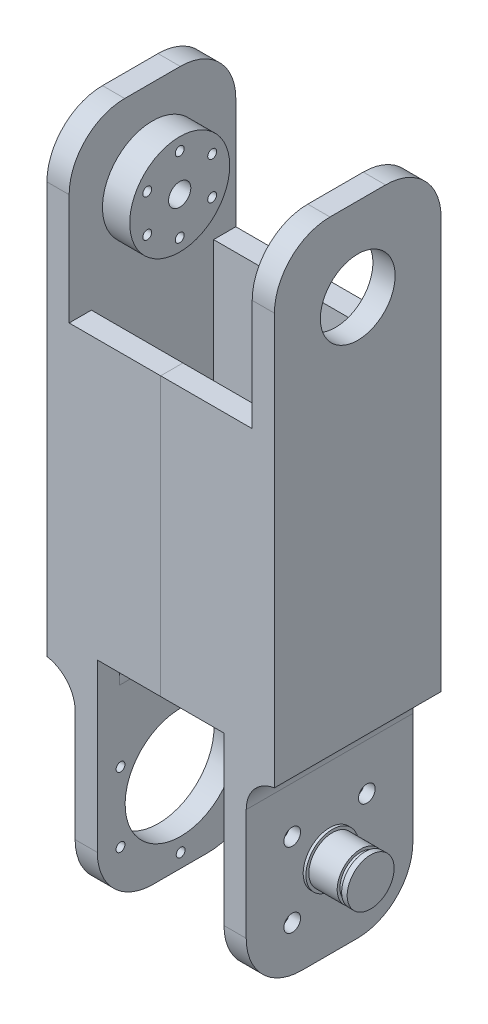
SolidWorks part; units mm, degrees
ref_plane "前视基准面" through (0, 0, 0) normal (0, 0, 1) x (1, 0, 0)
ref_plane "上视基准面" through (0, 0, 0) normal (0, 1, 0) x (1, 0, 0)
ref_plane "右视基准面" through (0, 0, 0) normal (1, 0, 0) x (0, 0, -1)
other "Configuration Table"
sketch "草图1" plane through (0, 0, 0) normal (1, 0, 0) x (0, 0, -1)
  line L1 (30, -80) -> (-30, -80)
  line L2 (30, -80) -> (30, 80)
  line L3 (30, 80) -> (-30, 80)
  line L4 (-30, -80) -> (-30, 80)
  line L5 (30, -80) -> (-30, 80) construction
  line L6 (30, 80) -> (-30, -80) construction
  point P0 (0, 0)
  dimension "D1" = 160
  dimension "D2" = 60
extrude "凸台-拉伸1" add sketch "草图1" along normal blind 8
sketch "草图2" plane through (8, 0, 0) normal (1, 0, 0) x (0, 0, -1)
  line L1 (30, 80) -> (-30, 80) construction
  circle A0 centre (0, 50) radius 13.5 construction
  circle A2 centre (0, 63.5) radius 1.6
  circle A4 centre (11.6913, 56.75) radius 1.6
  circle A5 centre (11.6913, 43.25) radius 1.6
  circle A6 centre (0, 36.5) radius 1.6
  circle A7 centre (-11.6913, 43.25) radius 1.6
  circle A8 centre (-11.6913, 56.75) radius 1.6
  circle A12 centre (0, 50) radius 4
  point P6 (0, 80)
  point P26 (0, 50)
  dimension "D3" = 27
  dimension "D7" = 3.2
  dimension "D11" = 8
  dimension "D2" = 30
  dimension "D9" = 6
extrude "切除-拉伸1" cut sketch "草图2" against normal through all
sketch "草图20" plane through (8, 0, 0) normal (1, 0, 0) x (0, 0, -1)
  circle A0 centre (0, 50) radius 18
  dimension "D1" = 36
extrude "凸台-拉伸7" add sketch "草图20" along normal blind 9.8
sketch "草图3" plane through (8, 0, 0) normal (1, 0, 0) x (0, 0, -1)
  line L0 (-30, 80) -> (-30, -80) construction
  line L1 (-22, -80) -> (-30, -80)
  line L2 (-22, -80) -> (-22, 20)
  line L3 (-22, 20) -> (-30, 20)
  line L4 (-30, -80) -> (-30, 20)
  line L5 (-22, -80) -> (-30, 20) construction
  line L6 (-22, 20) -> (-30, -80) construction
  line L7 (30, -80) -> (22, -80)
  line L8 (30, -80) -> (30, 20)
  line L9 (30, 20) -> (22, 20)
  line L10 (22, -80) -> (22, 20)
  line L11 (30, -80) -> (22, 20) construction
  line L12 (30, 20) -> (22, -80) construction
  line L13 (30, -80) -> (30, 80) construction
  line L14 (30, 80) -> (-30, 80) construction
  line L16 (-30, -80) -> (30, -80) construction
  point P0 (-26, -30)
  point P5 (26, -30)
  dimension "D1" = 60
  dimension "D3" = 60
  dimension "D5" = 8
  dimension "D6" = 8
extrude "凸台-拉伸2" add sketch "草图3" along normal blind 65.9
sketch "草图4" plane through (73.9, 0, 0) normal (1, 0, 0) x (0, 0, -1)
  line L0 (30, -80) -> (-30, 80) construction
  line L1 (30, -80) -> (-30, -80)
  line L2 (30, -80) -> (30, 80)
  line L3 (30, 80) -> (-30, 80)
  line L4 (-30, -80) -> (-30, 80)
  line L5 (30, -80) -> (-30, 80) construction
  line L6 (30, 80) -> (-30, -80) construction
  line L7 (30, 80) -> (-30, 80) construction
  point P0 (0, 0)
extrude "凸台-拉伸3" add sketch "草图4" along normal blind 8
sketch "草图9" plane through (73.9, 0, 0) normal (-1, 0, 0) x (0, 0, 1)
  circle A0 centre (0, 50) radius 13.45
  dimension "D1" = 26.9
extrude "切除-拉伸5" cut sketch "草图9" against normal up to next
sketch "草图11" plane through (0, 0, 30) normal (0, 0, 1) x (1, 0, 0)
  line L0 (0, 80) -> (0, -80) construction
  line L1 (0, -80) -> (18.15, -80)
  line L2 (0, -80) -> (0, -88)
  line L3 (0, -88) -> (18.15, -88)
  line L4 (18.15, -80) -> (18.15, -88)
  line L5 (81.9, -80) -> (63.75, -80)
  line L6 (81.9, -80) -> (81.9, -88)
  line L7 (81.9, -88) -> (63.75, -88)
  line L8 (63.75, -80) -> (63.75, -88)
  line L9 (81.9, 80) -> (81.9, -80) construction
  line L11 (18.15, -88) -> (10.15, -88)
  line L12 (18.15, -88) -> (18.15, -160)
  line L13 (18.15, -160) -> (10.15, -160)
  line L14 (10.15, -88) -> (10.15, -160)
  line L15 (63.75, -88) -> (71.75, -88)
  line L16 (63.75, -88) -> (63.75, -160)
  line L17 (63.75, -160) -> (71.75, -160)
  line L18 (71.75, -88) -> (71.75, -160)
  line M10 (0, -80) -> (81.9, -80)
  dimension "D1" = 8
  dimension "D2" = 8
  dimension "D3" = 45.6
  dimension "D4" = 72
  dimension "D5" = 72
  dimension "D6" = 8
  dimension "D7" = 8
extrude "凸台-拉伸4" add sketch "草图11" against normal blind 60 contours L3 L14 L13 L12 | L4 L2 L3 M10 | L8 L7 L6 M10 | L18 L7 L16 L17 region at (72.825, -84, 30) region at (9.075, -84, 30) region at (14.15, -124, 30) region at (67.75, -124, 30)
fillet "圆角1" radius 20 8 edges at (4, 80, -30) (4, 80, 30) (77.9, 80, -30) (77.9, 80, 30) (67.75, -160, -30) (67.75, -160, 30) (14.15, -160, -30) (14.15, -160, 30)
fillet "圆角2" radius 12 4 edges at (63.75, -80, 0) (18.15, -80, 0) (71.75, -88, 0) (10.15, -88, 0)
sketch "草图13" plane through (71.75, 0, 0) normal (1, 0, 0) x (0, 0, -1)
  line L0 (10, -160) -> (-10, -160) construction
  line L1 (0, -130) -> (13.435, -116.565) construction
  line L3 (0, -130) -> (0, -111) construction
  circle A0 centre (0, -130) radius 19 construction
  circle A1 centre (13.435, -116.565) radius 1.6
  circle A2 centre (13.435, -143.435) radius 1.6
  circle A3 centre (-13.435, -143.435) radius 1.6
  circle A4 centre (-13.435, -116.565) radius 1.6
  point P4 (0, -160)
  point P5 (0.0241, -160.1066)
  point P6 (0, 0)
  point P17 (0, -130)
  dimension "D1" = 38
  dimension "D3" = 3.2
  dimension "D2" = 30
  dimension "D5" = 45
  dimension "D4" = 4
extrude "切除-拉伸6" cut sketch "草图13" against normal up to next
sketch "草图12" plane through (10.15, 0, 0) normal (-1, 0, 0) x (0, 0, 1)
  circle A0 centre (0, -130) radius 25 construction
  circle A1 centre (0, -105) radius 1.6
  circle A2 centre (21.6506, -117.5) radius 1.6
  circle A3 centre (21.6506, -142.5) radius 1.6
  circle A4 centre (0, -155) radius 1.6
  circle A5 centre (-21.6506, -142.5) radius 1.6
  circle A6 centre (-21.6506, -117.5) radius 1.6
  circle A7 centre (0, -130) radius 20
  point P17 (0, -130)
  dimension "D1" = 50
  dimension "D2" = 3.2
  dimension "D4" = 40
  dimension "D3" = 6
sketch "草图14" plane through (71.75, 0, 0) normal (1, 0, 0) x (0, 0, -1)
  circle A0 centre (0, -130) radius 8.45
  dimension "D1" = 16.9
extrude "凸台-拉伸5" add sketch "草图14" along normal blind 14.8
ref_plane "基准面1" through (84.55, 0, 0) normal (1, 0, 0) x (0, 0, -1)
sketch "草图15" plane through (84.55, 0, 0) normal (1, 0, 0) x (0, 0, -1)
  circle A0 centre (0, -130) radius 8.45
  circle A1 centre (0, -130) radius 7.45
  dimension "D1" = 16.9
  dimension "D2" = 14.9
extrude "切除-拉伸7" cut sketch "草图15" against normal blind 1.6
extrude "切除-拉伸8" cut sketch "草图12" against normal up to next
sketch "草图16" plane through (0, 0, 0) normal (-1, 0, 0) x (0, 0, 1)
  circle A0 centre (0, 63.5) radius 3
  circle A1 centre (11.6913, 56.75) radius 3
  circle A2 centre (11.6913, 43.25) radius 3
  circle A3 centre (0, 36.5) radius 3
  circle A4 centre (-11.6913, 43.25) radius 3
  circle A5 centre (-11.6913, 56.75) radius 3
  point P17 (0, 50)
  dimension "D1" = 6
  dimension "D2" = 6
extrude "切除-拉伸9" cut sketch "草图16" against normal blind 4
sketch "草图17" plane through (10.15, 0, 0) normal (-1, 0, 0) x (0, 0, 1)
  circle A0 centre (0, -105) radius 3
  circle A1 centre (21.6506, -117.5) radius 3
  circle A2 centre (21.6506, -142.5) radius 3
  circle A3 centre (0, -155) radius 3
  circle A4 centre (-21.6506, -142.5) radius 3
  circle A5 centre (-21.6506, -117.5) radius 3
  point P15 (0, -130)
  dimension "D1" = 6
  dimension "D2" = 6
extrude "切除-拉伸10" cut sketch "草图17" against normal blind 4
sketch "草图18" plane through (71.75, 0, 0) normal (1, 0, 0) x (0, 0, -1)
  circle A0 centre (13.435, -116.565) radius 3
  circle A1 centre (13.435, -143.435) radius 3
  circle A2 centre (-13.435, -143.435) radius 3
  circle A3 centre (-13.435, -116.565) radius 3
  point P12 (0, -130)
  dimension "D1" = 6
  dimension "D2" = 4
extrude "切除-拉伸11" cut sketch "草图18" against normal blind 4
sketch "草图19" plane through (71.75, 0, 0) normal (1, 0, 0) x (0, 0, -1)
  circle A0 centre (0, -130) radius 9.5
  dimension "D1" = 19
extrude "凸台-拉伸6" add sketch "草图19" along normal blind 1
extrude "切除-拉伸12" cut sketch "草图2<3>" along normal up to next
sketch "草图2<3>" plane through (8, 0, 0) normal (1, 0, 0) x (0, 0, -1) same geometry as "草图2"
ref_plane "基准面2" through (40.95, 0, 0) normal (1, 0, 0) x (0, 0, -1)
split "分割1" trim tools "基准面2" bodies to split 126 resulting bodies 127 128
